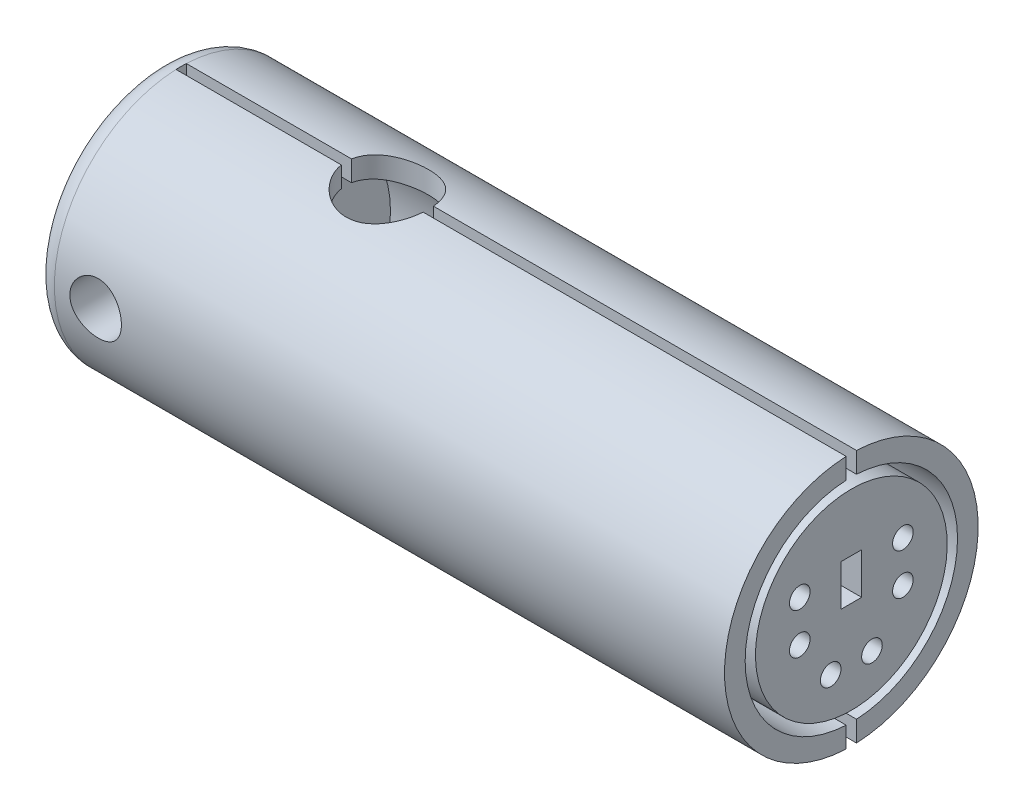
SolidWorks part; units mm, degrees
ref_plane "Спереди" through (0, 0, 0) normal (0, 0, 1) x (1, 0, 0)
ref_plane "Сверху" through (0, 0, 0) normal (0, 1, 0) x (1, 0, 0)
ref_plane "Справа" through (0, 0, 0) normal (1, 0, 0) x (0, 0, -1)
sketch "Эскиз1" plane through (0, 0, 0) normal (0, 0, 1) x (1, 0, 0)
  line L0 (0, 0) -> (0, 6.15)
  line L1 (0, 0) -> (33.5, 0) construction
  line L2 (0, 6.15) -> (33.5, 6.15)
  line L3 (33.5, 0) -> (33.5, 6.15)
  line L4 (0, 0) -> (33.5, 0)
  dimension "D1" = 6.15
  dimension "D2" = 33.5
revolve "Повернуть1" add sketch "Эскиз1" angle 360 about L1
sketch "Эскиз2" plane through (33.5, 0, 0) normal (1, 0, 0) x (0, 0, -1)
  circle A0 centre (0, 0) radius 5.15
  circle A1 centre (0, 0) radius 6.15 construction
  dimension "D1" = 1
extrude "Вырез-Вытянуть1" cut sketch "Эскиз2" against normal blind 27.5
sketch "Эскиз3" plane through (0, 0, 0) normal (-1, 0, 0) x (0, 0, 1)
  circle A0 centre (0, 0) radius 2.25
  dimension "D1" = 4.5
extrude "Вырез-Вытянуть2" cut sketch "Эскиз3" against normal through all
sketch "Эскиз4" plane through (0, 0, 0) normal (-1, 0, 0) x (0, 0, 1)
  line L0 (0, 0) -> (0, 6.15) construction
  line L1 (0, 0) -> (6.15, 0) construction
  circle A0 centre (0, 0) radius 6.15 construction
ref_plane "Плоскость1" through (0, 0, 0) normal (0, 0, 1) x (0, 1, 0)
ref_axis "Ось1" through (6, 0, 0) along (1, 0, 0)
sketch "Эскиз5" plane through (0, 0, 0) normal (0, 0, 1) x (0, 1, 0)
  line L0 (2.25, 0) -> (-2.25, 0) construction
  line L1 (2.25, 0) -> (-2.25, 0) construction
  line L2 (-2.25, -1) -> (-2.25, -5)
  line L3 (-2.25, -1) -> (-3, -1)
  line L4 (-2.25, -5) -> (-3, -5)
  line L5 (-3, -1) -> (-3, -5)
  line L6 (-2.25, -6) -> (2.25, -6) construction
  line L7 (-2.25, -6) -> (2.25, -6) construction
  line L8 (-2.25, 0) -> (-2.25, -6) construction
  dimension "D1" = 1
  dimension "D2" = 1
  dimension "D3" = 0.75
revolve "Вырез-Повернуть1" cut sketch "Эскиз5" angle 360 about axis through (6, 0, 0) along (1, 0, 0)
sketch "Эскиз6" plane through (0, 0, 0) normal (0, 0, 1) x (0, 1, 0)
  line L0 (-3, -1) -> (3, -1) construction
  line L1 (-3, -1) -> (3, -1) construction
  line L2 (3, -5) -> (-3, -5) construction
  line L3 (3, -5) -> (-3, -5) construction
  line L4 (0, -1) -> (0, -5) construction
  circle A0 centre (0, -3) radius 1.25
  dimension "D1" = 2.5
extrude "Вырез-Вытянуть3" cut sketch "Эскиз6" against normal through all and the other way through all
ref_plane "Плоскость2" through (0, 0, 0) normal (0, -1, 0) x (0, 0, 1)
sketch "Эскиз7" plane through (0, 0, 0) normal (0, -1, 0) x (0, 0, 1)
  line L0 (-5.15, -6) -> (5.15, -6) construction
  line L1 (-5.15, -6) -> (5.15, -6) construction
  line L2 (0, -6) -> (0, -11) construction
  circle A0 centre (0, -11) radius 2
  dimension "D1" = 4
  dimension "D2" = 5
extrude "Вырез-Вытянуть4" cut sketch "Эскиз7" against normal through all
fillet "Скругление1" radius 1 1 edges at (0, -6.15, 0)
ref_plane "Плоскость3" through (1, 0, 0) normal (1, 0, 0) x (0, 0, -1)
sketch "Эскиз8" plane through (33.5, 0, 0) normal (1, 0, 0) x (0, 0, -1)
  line L0 (0, 0) -> (0, -6.15) construction
  line L1 (0.25, -6.15) -> (-0.25, -6.15)
  line L2 (0.25, -6.15) -> (0.25, 6.15)
  line L3 (-0.25, -6.15) -> (-0.25, 6.15)
  line L4 (0.25, 6.15) -> (-0.25, 6.15)
  line L5 (0, -6.15) -> (0, 6.15) construction
  circle A0 centre (0, 0) radius 6.15 construction
  dimension "D1" = 0.5
extrude "Вырез-Вытянуть5" cut sketch "Эскиз8" against normal up to surface (32.5 mm away) up to plane "Плоскость3"
sketch "Эскиз9" plane through (33.5, 0, 0) normal (1, 0, 0) x (0, 0, -1)
  line L0 (0, -4.65) -> (0, 4.65) construction
  line L1 (-3.821, -2.65) -> (3.821, -2.65) construction
  line L2 (1, -4.5412) -> (1, 4.5412) construction
  line L3 (2.5, -2.65) -> (2.5, 3.9208) construction
  line L4 (-0.5, 1.85) -> (0.5, 1.85)
  line L5 (-0.5, 1.85) -> (-0.5, -0.15)
  line L6 (0.5, 1.85) -> (0.5, -0.15)
  line L7 (-0.5, -0.15) -> (0.5, -0.15)
  circle A0 centre (0, 0) radius 4.65
  arc A1 (-0.25, 5.1439) -> (-0.25, -5.1439) centre (0, 0) ccw construction
  circle A2 centre (1, -2.65) radius 0.5
  circle A3 centre (2.5, -0.65) radius 0.5
  circle A4 centre (2.5, 1.35) radius 0.5
  circle A5 centre (-2.5, 1.35) radius 0.5
  circle A6 centre (-2.5, -0.65) radius 0.5
  circle A7 centre (-1, -2.65) radius 0.5
  arc A8 (0.25, -5.1439) -> (0.25, 5.1439) centre (0, 0) ccw construction
  circle A9 centre (0, 0) radius 5.15 construction
  point P26 (0, 1.85)
  dimension "D1" = 0.5
  dimension "D4" = 1
  dimension "D6" = 2
  dimension "D2" = 2
  dimension "D3" = 1
  dimension "D5" = 2
  dimension "D7" = 1.5
  dimension "D8" = 1
  dimension "D9" = 2
  dimension "D10" = 2.5
extrude "Бобышка-Вытянуть1" add sketch "Эскиз9" against normal blind 12 separate body
sketch "Эскиз10" plane through (0, 0, 0) normal (0, 0, 1) x (0, 1, 0)
  line L0 (-4.65, -33.5) -> (4.65, -33.5) construction
  line L1 (-4.65, -33.5) -> (4.65, -33.5) construction
  line L2 (4.65, -21.5) -> (-4.65, -21.5) construction
  line L3 (4.65, -21.5) -> (-4.65, -21.5)
  line L4 (0, -33.5) -> (0, -21.5) construction
  circle A0 centre (0, -27.5) radius 1.5
  dimension "D1" = 3
extrude "Бобышка-Вытянуть2" add sketch "Эскиз10" along normal up to surface and the other way up to surface contours A0 region at (27.5, 0, 0) up to face at (1.7771, 0.2588, 6.1446) other way up to face at (1.7771, -0.2588, -6.1446)
sketch "Эскиз11" plane through (33.5, 0, 0) normal (1, 0, 0) x (0, 0, -1)
  arc A0 (0.25, -6.1449) -> (0.25, 6.1449) centre (0, 0) ccw construction
  circle A1 centre (0, 0) radius 6.15
